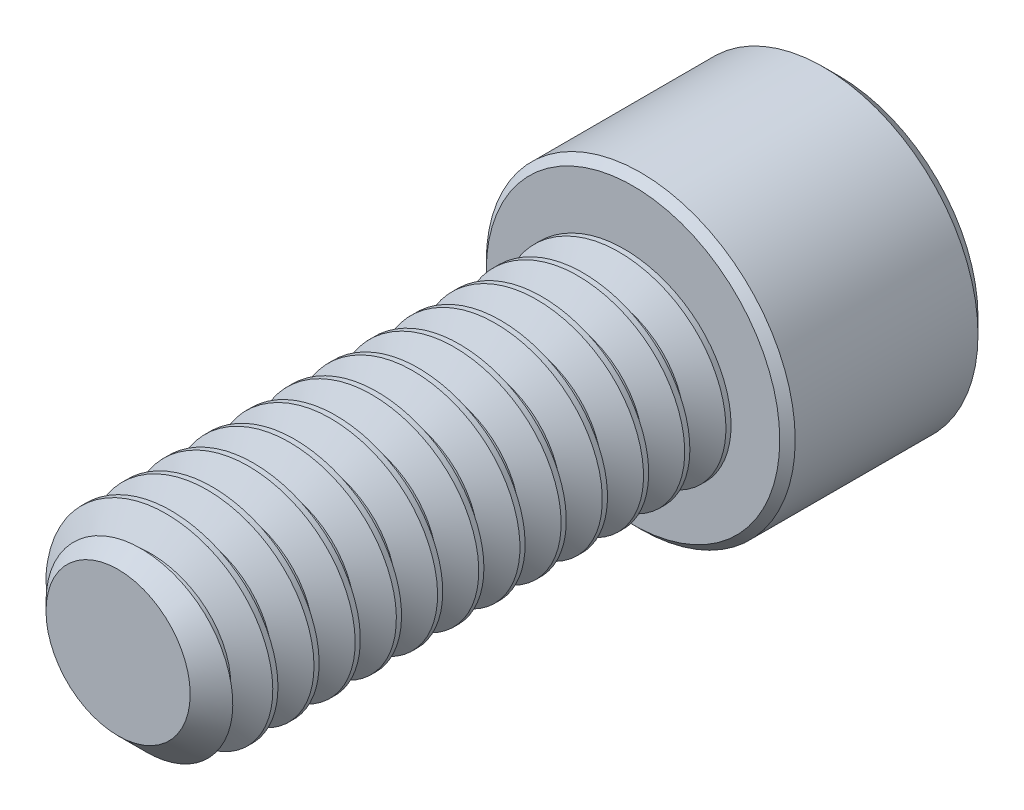
SolidWorks part; units mm, degrees
ref_plane "Front Plane" through (0, 0, 0) normal (0, 0, 1) x (1, 0, 0)
ref_plane "Top Plane" through (0, 0, 0) normal (0, 1, 0) x (1, 0, 0)
ref_plane "Right Plane" through (0, 0, 0) normal (1, 0, 0) x (0, 0, -1)
sketch "Sketch0" plane through (0, 0, 0) normal (1, 0, 0) x (0, 0, -1)
  line L0 (0, 0) -> (15.875, 0) construction
  point P2 (22.225, 0)
  point P4 (0, 0)
  dimension "D1" = 15.875
  dimension "D2" = 6.35
  dimension "Min Thread" = 0
sketch "Sketch1" plane through (0, 0, 0) normal (0, 0, 1) x (1, 0, 0)
  circle A0 centre (0, 0) radius 3.175
  dimension "OD" = 6.35
extrude "Extrude1" add sketch "Sketch1" against normal blind 15.875
sketch "Sketch2" plane through (0, 0, 0) normal (0, 0, 1) x (1, 0, 0)
  circle A0 centre (0, 0) radius 3.175 construction
  circle A1 centre (0, 0) radius 3.175
curve "Helix/Spiral1" pitch 1.27 height 17.145 turns 13.5 parameters "pitch"=1.27
chamfer "Chamfer3" distance 0.9525 angle 45 1 edges at (3.175, 0, 0)
sketch "Sketch3" plane through (0, 0, 0) normal (1, 0, 0) x (0, 0, -1)
  line L0 (-1.1113, 3.175) -> (-0.635, 2.3501)
  line L1 (-0.635, 2.3501) -> (-0.4763, 2.3501)
  line L2 (-0.4763, 2.3501) -> (0, 3.175)
  line L3 (-1.1113, 3.175) -> (0, 3.175)
  line L4 (-0.5556, 3.175) -> (-0.5556, 2.3501) construction
  line L5 (-0.8731, 2.7626) -> (-0.2381, 2.7626) construction
  line L6 (0, 3.175) -> (0, -3.175) construction
  dimension "D1" = 0.1588
  dimension "D2" = 0.635
  dimension "D3" = 60
sweep "Cut-Sweep1" cut profiles "Sketch3" path "Helix/Spiral1"
sketch "Sketch5" plane through (0, 0, 0) normal (1, 0, 0) x (0, 0, -1)
  line L0 (15.875, -2.2654) -> (15.875, 2.3728) construction
  line L1 (15.875, 3.175) -> (0, 3.175)
  line L2 (15.875, 3.175) -> (15.875, 0)
  line L3 (15.875, 0) -> (-1.1556, 0)
  line L4 (0, 0) -> (15.875, 0) construction
  line L5 (0, 3.175) -> (-1.1556, 0)
  line L6 (0, 0) -> (18.415, 0) construction
  dimension "D1" = 70
  dimension "D3" = 2.54
revolve "partially thread" [suppressed] add sketch "Sketch5" angle 360 about L6
sketch "Sketch6" plane through (0, 0, -15.875) normal (0, 0, -1) x (-1, 0, 0)
  circle A0 centre (0, 0) radius 4.7625
  dimension "head dia" = 9.525
extrude "Extrude2" add sketch "Sketch6" along normal blind 6.35
sketch "Sketch7" plane through (0, 0, -22.225) normal (0, 0, -1) x (-1, 0, 0)
  line L1 (0, 2.7496) -> (-2.3813, 1.3748)
  line L2 (-2.3813, 1.3748) -> (-2.3813, -1.3748)
  line L3 (-2.3813, -1.3748) -> (0, -2.7496)
  line L4 (0, -2.7496) -> (2.3813, -1.3748)
  line L5 (2.3813, -1.3748) -> (2.3813, 1.3748)
  line L6 (2.3813, 1.3748) -> (0, 2.7496)
  circle A0 centre (0, 0) radius 2.3813 construction
  dimension "hex dia" = 4.7625
extrude "Cut-Extrude1" cut sketch "Sketch7" against normal blind 3.5719
sketch "Sketch8" plane through (0, 0, -22.225) normal (0, 0, -1) x (-1, 0, 0)
  circle A0 centre (0, 0) radius 2.7496
extrude "Cut-Extrude2" cut sketch "Sketch8" against normal through all draft 45
chamfer "Chamfer1" distance 0.4763 angle 45 1 edges at (-4.7625, 0, -22.225)
chamfer "Chamfer2" distance 0.2381 angle 45 1 edges at (-4.7625, 0, -15.875)
sketch "Sketch9" plane through (0, 0, 0) normal (1, 0, 0) x (0, 0, -1)
  line L0 (0, 3.175) -> (0, -3.175) construction
  line L1 (3.175, 3.175) -> (3.175, -3.175) construction
  line L2 (22.225, 4.7625) -> (22.225, -4.7625) construction
  line L3 (15.875, 4.7625) -> (15.875, -4.7625) construction
  line L4 (15.875, 4.5244) -> (15.875, -4.5244) construction
  line L5 (22.225, -4.2863) -> (22.225, 4.2863) construction
  line L6 (15.875, -4.7625) -> (15.875, 4.7625) construction
  line L7 (0, 2.2225) -> (0, -2.2225) construction
  line L8 (-1.1113, 3.175) -> (0, 3.175) construction
  line L9 (3.175, 0) -> (0, 0) construction
  dimension "D1" = 3.175
equation "\"D3@Helix/Spiral1\" = \"screw length@Extrude1\"+\"pitch@Helix/Spiral1\""
equation "\"D1@Sketch3\" = \"pitch@Helix/Spiral1\"*.125"
equation "\"D2@Sketch3\" = \"pitch@Helix/Spiral1\"*.5"
equation "\"D1@Cut-Extrude1\" = \"hex dia@Sketch7\"*.75"
equation "\"D1@Chamfer1\" = \"head dia@Sketch6\"*.05"
equation "\"D1@Sketch9\" = \"pitch@Helix/Spiral1\"*2.50"
equation "\"D1@Chamfer2\" = \"D1@Chamfer1\"/2"
equation "\"D1@Chamfer3\" = \"pitch@Helix/Spiral1\"*.750"
equation "\"D1@Sketch0\" = \"screw length@Extrude1\""
equation "\"D2@Sketch0\" = \"head depth@Extrude2\""
